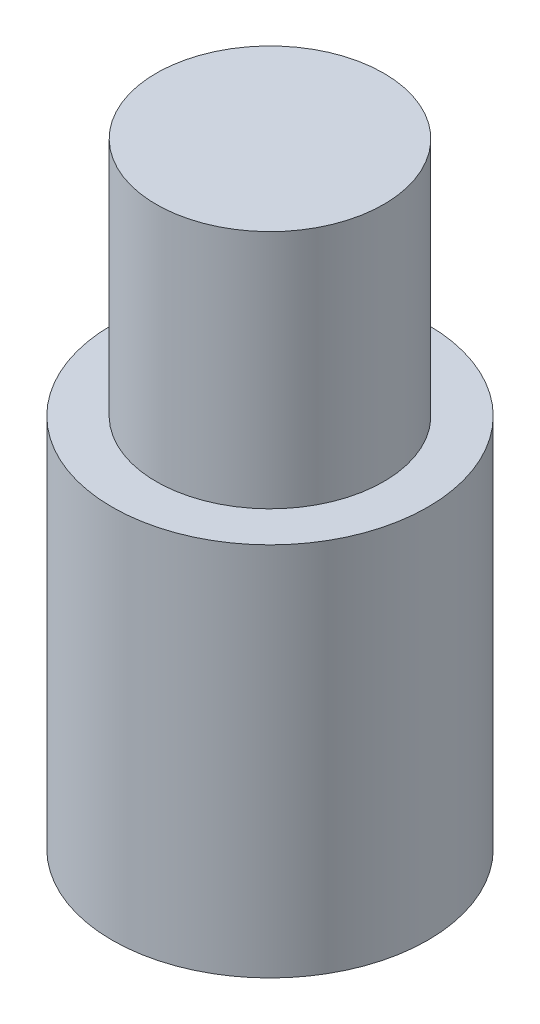
SolidWorks part; units mm, degrees
ref_plane "Front Plane" through (0, 0, 0) normal (0, 0, 1) x (1, 0, 0)
ref_plane "Top Plane" through (0, 0, 0) normal (0, 1, 0) x (1, 0, 0)
ref_plane "Right Plane" through (0, 0, 0) normal (1, 0, 0) x (0, 0, -1)
sketch "Sketch2" plane through (0, 0, 0) normal (0, 0, 1) x (1, 0, 0)
  line L0 (0, 0) -> (0, 26.035)
  line L1 (0, 26.035) -> (4.8133, 26.035)
  line L2 (0, 0) -> (6.6802, 0)
  line L3 (6.6802, 0) -> (6.6802, 15.875)
  line L4 (6.6802, 15.875) -> (4.8133, 15.875)
  line L5 (4.8133, 26.035) -> (4.8133, 15.875)
  line L6 (0.1487, 0) -> (4.7625, 0)
  line L7 (4.7625, 0) -> (4.7625, 12.7)
  line L8 (4.7625, 12.7) -> (0, 12.7)
  dimension "D1" = 12.7
  dimension "D2" = 6.6802
  dimension "D3" = 4.8133
  dimension "D4" = 10.16
  dimension "D5" = 4.7625
  dimension "D6" = 15.875
revolve "Revolve3" add sketch "Sketch2" angle 360 about L0 region at (3.4708, 15.6927, 0)
